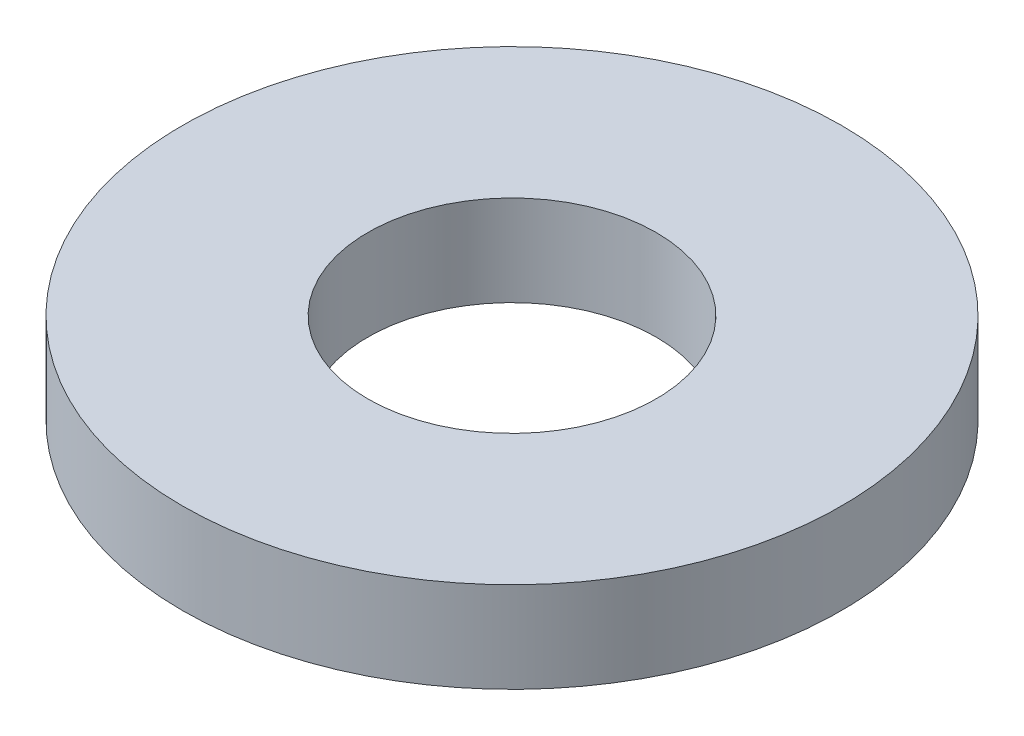
SolidWorks part; units mm, degrees
ref_plane "Front Plane" through (0, 0, 0) normal (0, 0, 1) x (1, 0, 0)
ref_plane "Top Plane" through (0, 0, 0) normal (0, 1, 0) x (1, 0, 0)
ref_plane "Right Plane" through (0, 0, 0) normal (1, 0, 0) x (0, 0, -1)
sketch "Sketch1" plane through (0, 0, 0) normal (0, 1, 0) x (1, 0, 0)
  circle A0 centre (0, 0) radius 80
  dimension "FLANGE_OD" = 160
extrude "Boss-Extrude1" add sketch "Sketch1" along normal blind 22
sketch "Sketch2" plane through (0, 0, 0) normal (0, 1, 0) x (1, 0, 0)
  circle A0 centre (0, 0) radius 35
  dimension "BORE_D" = 70
extrude "Cut-Extrude1" cut sketch "Sketch2" along normal through all
sketch "Sketch3" plane through (0, 22, 0) normal (0, 1, 0) x (1, 0, 0)
  circle A0 centre (0, 0) radius 25.7573 construction
  circle A1 centre (-25.7573, 0) radius 3.4655
  dimension "BOLT_D" = 6.9311
  dimension "BOLT_PCD" = 51.5147
extrude "Cut-Extrude2" cut sketch "Sketch3" against normal blind 13.9198 rebuild error yes
pattern_circular "CirPattern1" count 4 over 360 rebuild error yes
